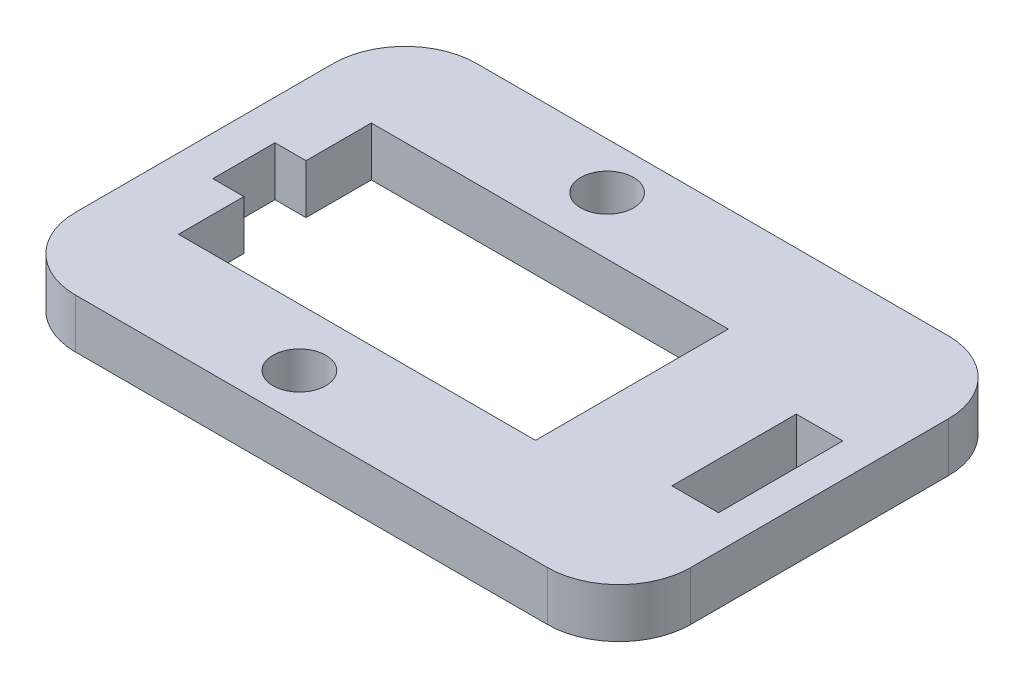
SolidWorks part; units mm, degrees
material "Acrylic (Medium-high impact)"
ref_plane "Front Plane" through (0, 0, 0) normal (0, 0, 1) x (1, 0, 0)
ref_plane "Top Plane" through (0, 0, 0) normal (0, 1, 0) x (1, 0, 0)
ref_plane "Right Plane" through (0, 0, 0) normal (1, 0, 0) x (0, 0, -1)
sketch "Sketch1" plane through (0, 0, 0) normal (0, 1, 0) x (1, 0, 0)
  line L0 (-17.9277, 8.4795) -> (5.0313, 8.4795)
  line L1 (5.0313, 8.4795) -> (5.0313, -3.9215)
  line L2 (5.0313, -3.9215) -> (-17.9277, -3.9215)
  line L3 (-17.9277, -3.9215) -> (-17.9277, 0.2796)
  line L4 (-17.9277, 0.2796) -> (-19.9237, 0.2796)
  line L5 (-19.9237, 0.2796) -> (-19.9237, 4.2784)
  line L6 (-19.9237, 4.2784) -> (-17.9277, 4.2784)
  line L7 (-17.9277, 4.2784) -> (-17.9277, 8.4795)
  line L8 (-17.8539, 15.1785) -> (12.4964, 15.1785)
  line L9 (17.1063, 10.5686) -> (17.1063, -6.0107)
  line L10 (12.4964, -10.6205) -> (-17.8539, -10.6205)
  line L11 (-22.4637, -6.0107) -> (-22.4637, 10.5686)
  line L12 (11.9543, 5.9325) -> (14.9493, 5.9325)
  line L13 (14.9493, 5.9325) -> (14.9493, -2.0675)
  line L14 (14.9493, -2.0675) -> (11.9543, -2.0675)
  line L15 (11.9543, -2.0675) -> (11.9543, 5.9325)
  line L16 (-8.1617, 12.1795) -> (-4.7617, 12.1795) construction
  line L17 (-8.153, -7.6214) -> (-4.753, -7.6217) construction
  line L18 (-22.4637, 2.279) -> (17.1063, 2.279) construction
  arc A0 (-17.8539, 15.1785) -> (-22.4637, 10.5686) centre (-17.8539, 10.5686) ccw
  arc A1 (-22.4637, -6.0107) -> (-17.8539, -10.6205) centre (-17.8539, -6.0107) ccw
  arc A2 (12.4964, -10.6205) -> (17.1063, -6.0107) centre (12.4964, -6.0107) ccw
  arc A3 (17.1063, 10.5686) -> (12.4964, 15.1785) centre (12.4964, 10.5686) ccw
  circle A4 centre (-6.4617, 12.1795) radius 1.7
  circle A5 centre (-6.453, -7.6215) radius 1.7
  point P34 (0, 0)
  point P35 (0, 0)
  point P36 (0, 0)
  point P37 (0, 0)
  point P38 (0, 0)
  dimension "D1" = 3.4
  dimension "D7" = 19.801
  dimension "D8" = 9.9005
  dimension "D14" = 16.0107
  dimension "D16" = 4.6099
  dimension "D17" = 16.002
  dimension "D2" = 25.799
  dimension "D3" = 39.57
  dimension "D4" = 12.401
  dimension "D5" = 6.2005
  dimension "D6" = 22.959
  dimension "D9" = 2.995
  dimension "D10" = 8
  dimension "D11" = 6.923
  dimension "D12" = 2.54
  dimension "D13" = 8.553
  dimension "D15" = 1.996
extrude "Boss-Extrude1" add sketch "Sketch1" along normal blind 3.175
